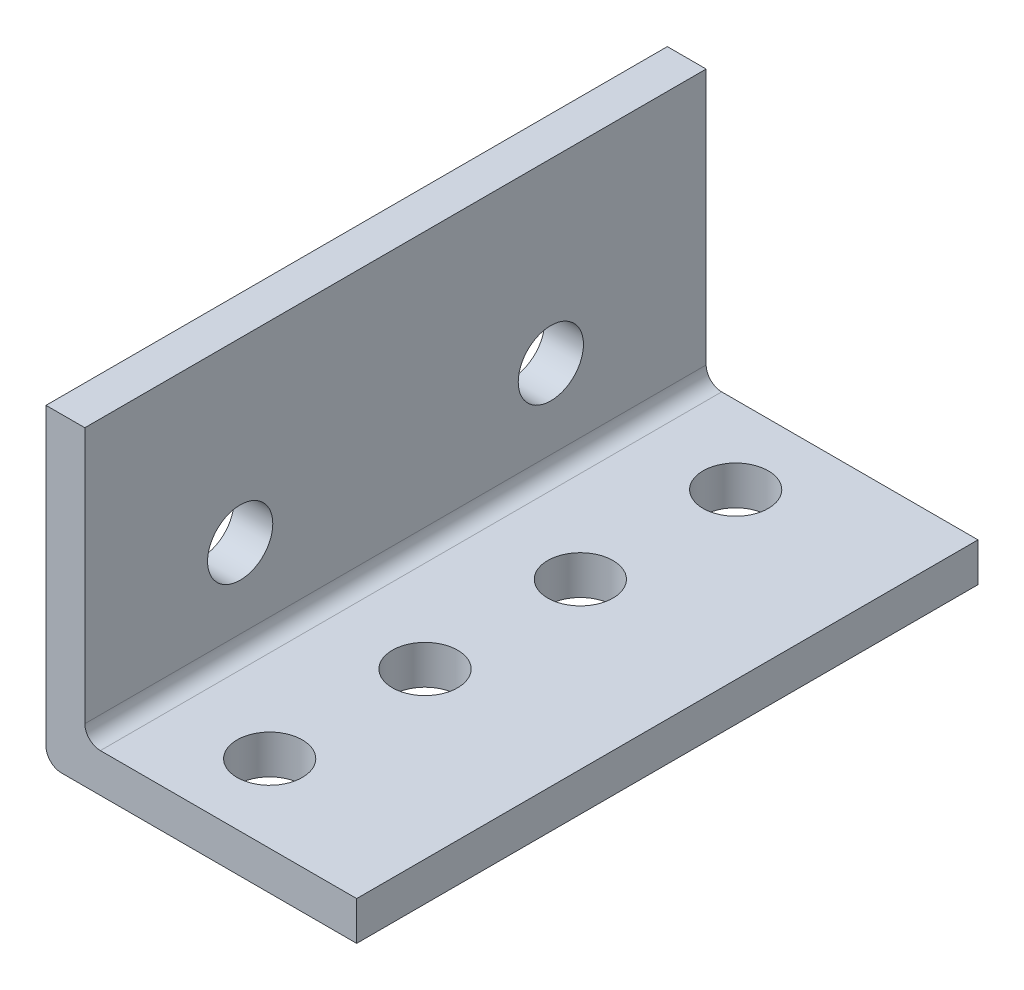
SolidWorks part; units mm, degrees
ref_plane "Front Plane" through (0, 0, 0) normal (0, 0, 1) x (1, 0, 0)
ref_plane "Top Plane" through (0, 0, 0) normal (0, 1, 0) x (1, 0, 0)
ref_plane "Right Plane" through (0, 0, 0) normal (1, 0, 0) x (0, 0, -1)
sketch "Sketch1" plane through (0, 0, 0) normal (0, 0, 1) x (1, 0, 0)
  line L1 (0, -22.225) -> (22.225, -22.225)
  line L2 (22.225, -22.225) -> (22.225, -25.4)
  line L3 (22.225, -25.4) -> (-3.175, -25.4)
  line L4 (-3.175, -25.4) -> (-3.175, 0)
  line L5 (-3.175, 0) -> (0, 0)
  line L6 (0, 0) -> (0, -22.225)
  dimension "D1" = 3.175
  dimension "D2" = 25.4
  dimension "D3" = 22.225
extrude "Boss-Extrude1" add sketch "Sketch1" along normal blind 50.8
sketch "Sketch2" plane through (0, 0, 0) normal (1, 0, 0) x (0, 0, -1)
  line L0 (-25.4, -11.1125) -> (-25.4, 0) construction
  line L1 (-38.1, -11.1125) -> (-38.1, -14.478)
  line L2 (-38.1, -11.1125) -> (-12.7, -11.1125) construction
  line L3 (-50.8, 0) -> (0, 0) construction
  line L4 (-12.7, -11.1125) -> (-12.7, -14.478)
  line L6 (-25.4, -11.1125) -> (-25.4, -22.225) construction
  line L7 (-50.8, -22.225) -> (0, -22.225) construction
  circle A2 centre (-38.1, -14.478) radius 2.667
  circle A3 centre (-12.7, -14.478) radius 2.667
  dimension "D1" = 25.4
extrude "Cut-Extrude1" cut sketch "Sketch2" against normal through all both and the other way through all contours A2 | A3 region at (0, -16.3105, 39.9325) region at (0, -16.3105, 14.5325)
sketch "Sketch3" plane through (0, -22.225, 0) normal (0, 1, 0) x (1, 0, 0)
  line L0 (22.225, -25.4) -> (8.763, -25.4)
  line L1 (22.225, -50.8) -> (22.225, 0) construction
  line L2 (8.763, -19.05) -> (8.763, -31.75)
  line L3 (8.763, -31.75) -> (8.763, -44.45)
  circle A0 centre (8.763, -44.45) radius 2.667
  circle A1 centre (8.763, -31.75) radius 2.667
  circle A2 centre (8.763, -19.05) radius 2.667
  circle A3 centre (8.763, -6.35) radius 2.667
  point P6 (8.763, -25.4)
  dimension "D1" = 4
extrude "Cut-Extrude2" cut sketch "Sketch3" against normal up to surface (3.175 mm away) contours A0 | L2 A1 L3 | A2 | A3 | L3 A1 L2 region at (10.5955, -22.225, 42.6175) region at (9.8949, -22.225, 31.75) region at (7.6311, -22.225, 31.75) region at (6.9305, -22.225, 17.2175) region at (8.763, -22.225, 6.35) up to face at (9.525, -25.4, 25.4)
fillet "Fillet1" radius 1.27 1 edges at (0, -22.225, 25.4)
fillet "Fillet2" radius 1.27 1 edges at (-3.175, -25.4, 25.4)
